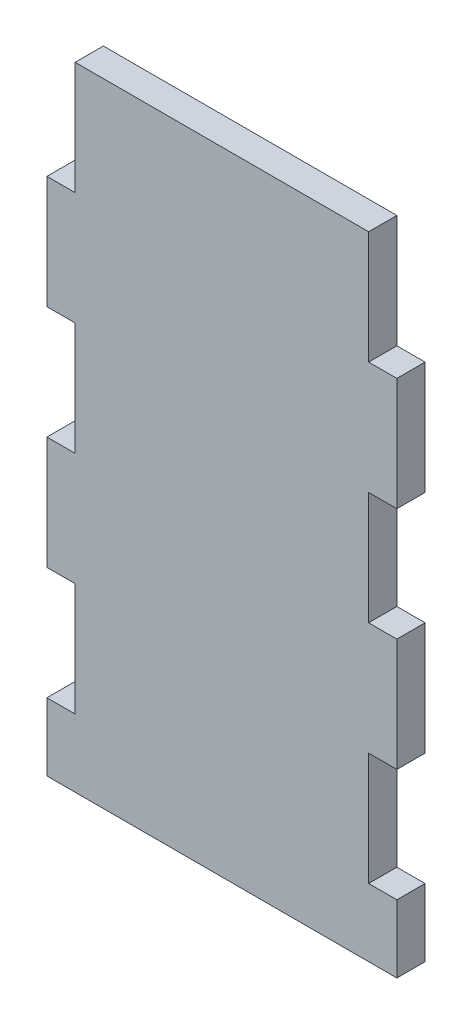
SolidWorks part; units mm, degrees
ref_plane "Front Plane" through (0, 0, 0) normal (0, 0, 1) x (1, 0, 0)
ref_plane "Top Plane" through (0, 0, 0) normal (0, 1, 0) x (1, 0, 0)
ref_plane "Right Plane" through (0, 0, 0) normal (1, 0, 0) x (0, 0, -1)
sketch "Sketch1" plane through (0, 0, 0) normal (0, 0, 1) x (1, 0, 0)
  line L0 (-33.02, 45.72) -> (-39.37, 45.72)
  line L1 (-39.37, 71.12) -> (39.37, 71.12)
  line L2 (-39.37, 71.12) -> (-39.37, -71.12)
  line L3 (-39.37, -71.12) -> (39.37, -71.12)
  line L4 (39.37, 71.12) -> (39.37, -71.12)
  line L5 (-39.37, 71.12) -> (-33.02, 71.12)
  line L6 (-39.37, 71.12) -> (-39.37, -71.12)
  line L7 (-39.37, -71.12) -> (-33.02, -71.12)
  line L8 (-33.02, 71.12) -> (-33.02, -71.12)
  line L9 (39.37, 71.12) -> (33.02, 71.12)
  line L10 (39.37, 71.12) -> (39.37, -71.12)
  line L11 (39.37, -71.12) -> (33.02, -71.12)
  line L12 (33.02, 71.12) -> (33.02, -71.12)
  line L13 (39.37, 45.72) -> (33.02, 45.72)
  line L14 (-33.02, 20.32) -> (-39.37, 20.32)
  line L15 (39.37, 20.32) -> (33.02, 20.32)
  line L16 (-33.02, -5.08) -> (-39.37, -5.08)
  line L17 (39.37, -5.08) -> (33.02, -5.08)
  line L18 (-33.02, -30.48) -> (-39.37, -30.48)
  line L19 (39.37, -30.48) -> (33.02, -30.48)
  line L20 (-33.02, -55.88) -> (-39.37, -55.88)
  line L21 (39.37, -55.88) -> (33.02, -55.88)
  line L22 (-33.02, 45.72) -> (-33.02, 20.32) construction
  point P4 (0, 71.12)
  point P6 (-39.37, 0)
  point P15 (-36.195, 45.72)
  dimension "D1" = 78.74
  dimension "D2" = 142.24
  dimension "D3" = 6.35
  dimension "D4" = 6.35
  dimension "D5" = 25.4
  dimension "D6" = 5
  dimension "D7" = 25.4
extrude "Boss-Extrude1" add sketch "Sketch1" along normal blind 6.35 contours L12 L1 L8 L3 | L14 L8 L0 L2 | L18 L8 L16 L2 | L8 L20 L2 L3 | L10 L21 L12 L3 | L19 L10 L17 L12 | L15 L10 L13 L12 region at (-36.195, 33.02, 0) region at (0, 0, 0) region at (-36.195, -17.78, 0) region at (36.195, 33.02, 0) region at (-36.195, -63.5, 0) region at (36.195, -17.78, 0) region at (36.195, -63.5, 0)
